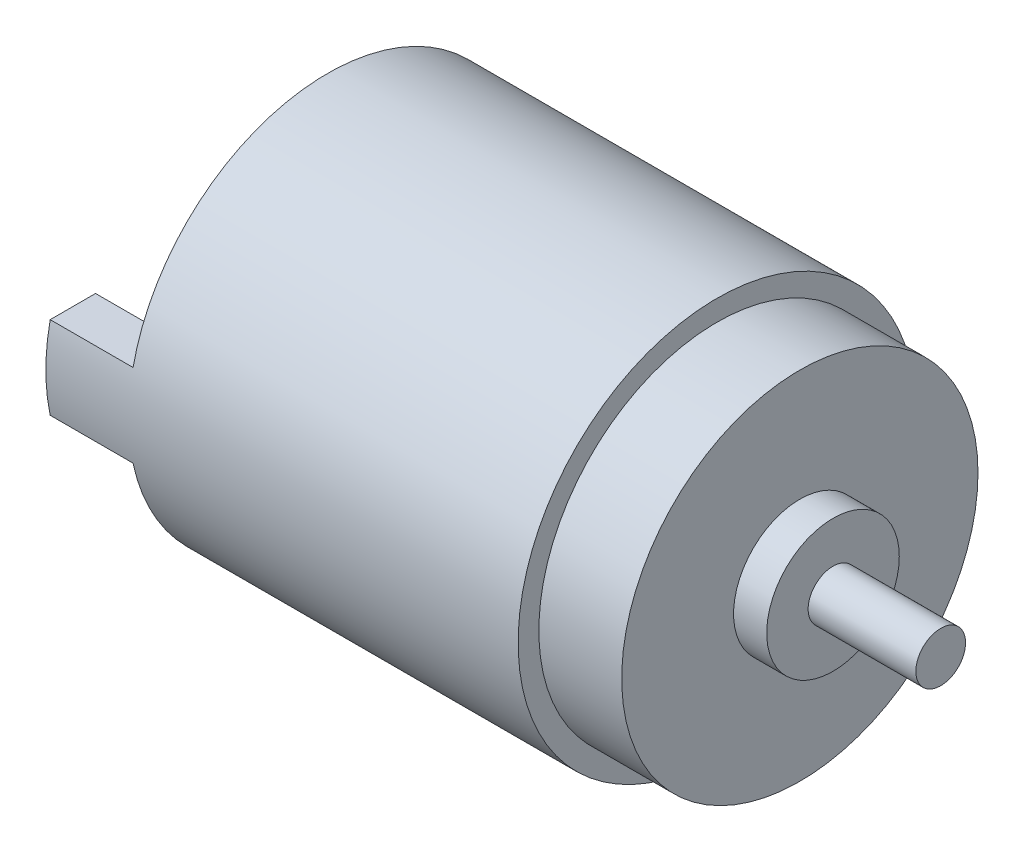
SolidWorks part; units mm, degrees
ref_plane "前视基准面" through (0, 0, 0) normal (0, 0, 1) x (1, 0, 0)
ref_plane "上视基准面" through (0, 0, 0) normal (0, 1, 0) x (1, 0, 0)
ref_plane "右视基准面" through (0, 0, 0) normal (1, 0, 0) x (0, 0, -1)
sketch "草图1" plane through (0, 0, 0) normal (1, 0, 0) x (0, 0, -1)
  circle A0 centre (0, 0) radius 12
  dimension "D1" = 24
extrude "凸台-拉伸1" add sketch "草图1" along normal blind 23.5
sketch "草图2" plane through (23.5, 0, 0) normal (1, 0, 0) x (0, 0, -1)
  circle A0 centre (0, 0) radius 1.5
extrude "凸台-拉伸2" add sketch "草图2" along normal blind 13.5
sketch "草图3" plane through (23.5, 0, 0) normal (1, 0, 0) x (0, 0, -1)
  circle A0 centre (0, 0) radius 10.75
  dimension "D1" = 21.5
extrude "凸台-拉伸3" add sketch "草图3" along normal blind 5
sketch "草图4" plane through (28.5, 0, 0) normal (1, 0, 0) x (0, 0, -1)
  circle A0 centre (0, 0) radius 4
  dimension "D1" = 8
extrude "凸台-拉伸4" add sketch "草图4" along normal blind 2
sketch "草图5" plane through (0, 0, 0) normal (-1, 0, 0) x (0, 0, 1)
  line L0 (-2.0616, -4) -> (2.0616, -4)
  arc A0 (2.0616, -4) -> (-2.0616, -4) centre (0, 0) ccw
  point P5 (0, 0)
  dimension "D1" = 9
  dimension "D2" = 4
extrude "凸台-拉伸5" add sketch "草图5" along normal blind 2
sketch "草图6" plane through (0, 0, 0) normal (-1, 0, 0) x (0, 0, 1)
  line L0 (0, 0) -> (14.3141, 0) construction
  line L2 (9, 2.5) -> (11.7367, 2.5)
  line L3 (9, 2.5) -> (9, -2.5)
  line L4 (9, -2.5) -> (11.7367, -2.5)
  circle A0 centre (0, 0) radius 12
  circle A1 centre (0, 0) radius 12 construction
  point P10 (11.7367, 2.5)
  point P11 (11.7367, -2.5)
  point P12 (11.738, 2.0918)
  point P13 (0, 0)
  point P14 (0, 0)
  point P16 (0, 0)
  point P17 (0, 0)
  circle M8 centre (0, 0) radius 12
  dimension "D1" = 3
  dimension "D2" = 5
extrude "凸台-拉伸6" add sketch "草图6" along normal blind 5 contours L3 L0 A0 L2 | L0 L3 L4 M8 region at (0, 1.2312, 10.4574) region at (0, -1.2312, 10.4574)
mirror "镜向1" about plane through (0, 0, 0) normal (0, 0, 1) of "凸台-拉伸6"
